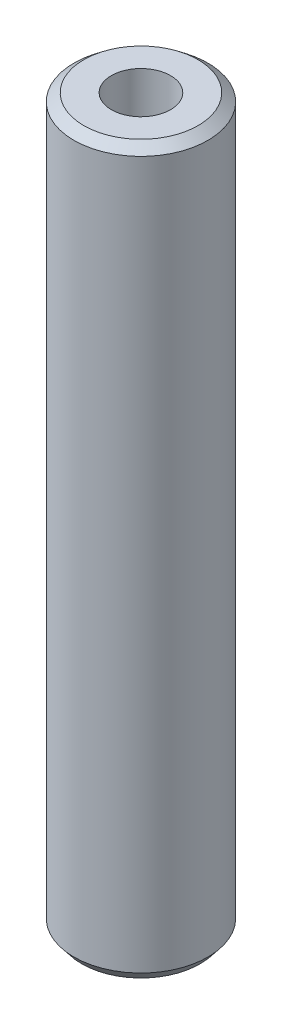
SolidWorks part; units mm, degrees
ref_plane "Front Plane" through (0, 0, 0) normal (0, 0, 1) x (1, 0, 0)
ref_plane "Top Plane" through (0, 0, 0) normal (0, 1, 0) x (1, 0, 0)
ref_plane "Right Plane" through (0, 0, 0) normal (1, 0, 0) x (0, 0, -1)
sketch "Sketch1" plane through (0, 0, 0) normal (0, 1, 0) x (1, 0, 0)
  circle A0 centre (0, 0) radius 17.5
  dimension "SHAFT_OD" = 35
extrude "Boss-Extrude1" add sketch "Sketch1" along normal blind 189.3834
sketch "Sketch2" plane through (0, 0, 0) normal (0, 1, 0) x (1, 0, 0)
  circle A0 centre (0, 0) radius 7.7282
  dimension "BORE_D" = 15.4564
extrude "Cut-Extrude1" cut sketch "Sketch2" along normal through all
chamfer "Chamfer1" distance 2.0482 angle 51.488 2 edges at (0, 189.3834, 17.5) (0, 0, 17.5) first distance on face at (0, 189.3834, 17.5) first distance on face at (0, 0, 7.7282)
